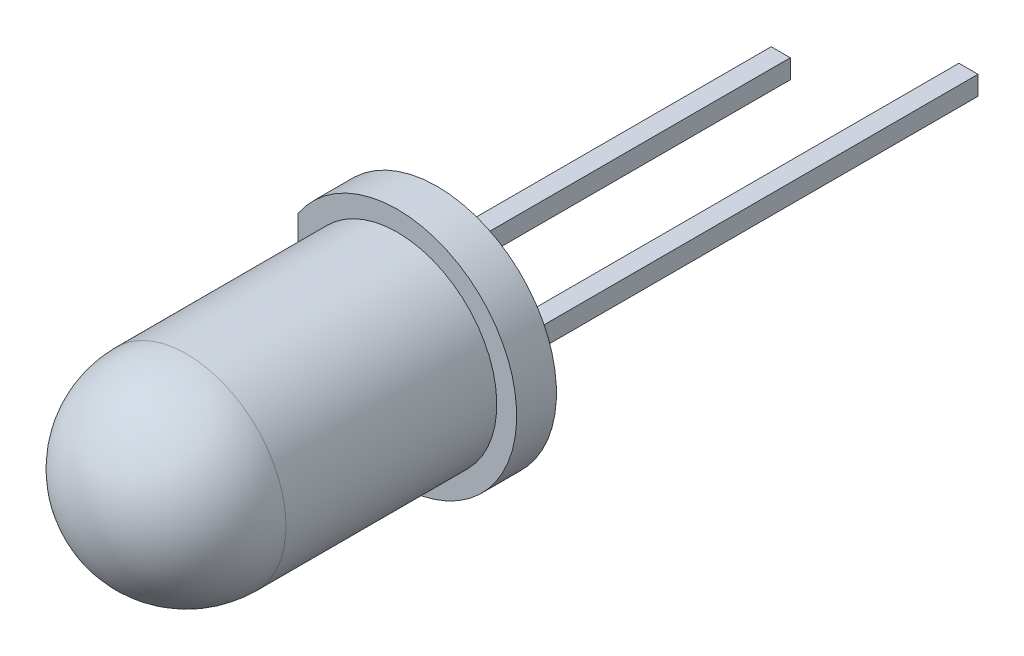
SolidWorks part; units mm, degrees
ref_plane "Plano frontal" through (0, 0, 0) normal (0, 0, 1) x (1, 0, 0)
ref_plane "Plano superior" through (0, 0, 0) normal (0, 1, 0) x (1, 0, 0)
ref_plane "Plano direito" through (0, 0, 0) normal (1, 0, 0) x (0, 0, -1)
sketch "Esboço1" plane through (0, 0, 0) normal (0, 0, 1) x (1, 0, 0)
  circle A0 centre (0, 0) radius 3
  dimension "D1" = 6
extrude "Ressalto-extrusão1" add sketch "Esboço1" along normal blind 1
sketch "Esboço3" plane through (0, 0, 0) normal (1, 0, 0) x (0, 0, -1)
  line L0 (-1, 0) -> (-8.8, 0)
  line L1 (-1, 3) -> (-1, -3) construction
  line L2 (-6.3, 2.5) -> (-1, 2.5)
  line L3 (-1, 0) -> (-1, 2.5)
  arc A0 (-8.8, 0) -> (-6.3, 2.5) centre (-6.3, 0) cw
  dimension "D1" = 2.5
  dimension "D2" = 7.8
revolve "Revolução1" add sketch "Esboço3" angle 360 about L0
sketch "Esboço4" plane through (0, 0, 0) normal (0, 0, -1) x (-1, 0, 0)
  line L0 (2.5, 1.6583) -> (2.5, -1.6583)
  circle A0 centre (0, 0) radius 3 construction
  arc A1 (2.5, -1.6583) -> (2.5, 1.6583) centre (0, 0) ccw
  circle A2 centre (0, 0) radius 2.5 construction
extrude "Corte-extrusão1" cut sketch "Esboço4" against normal up to surface (1 mm away) up to face at (2.5, 0, 1)
sketch "Esboço5" plane through (0, 0, 0) normal (0, 0, -1) x (-1, 0, 0)
  line L0 (-1.12, 0) -> (1.12, 0) construction
  line L1 (-1.6, -0.24) -> (-1.12, -0.24)
  line L2 (-1.6, -0.24) -> (-1.6, 0.24)
  line L3 (-1.6, 0.24) -> (-1.12, 0.24)
  line L4 (-1.12, -0.24) -> (-1.12, 0.24)
  line L5 (1.12, -0.24) -> (1.6, -0.24)
  line L6 (1.12, -0.24) -> (1.12, 0.24)
  line L7 (1.12, 0.24) -> (1.6, 0.24)
  line L8 (1.6, -0.24) -> (1.6, 0.24)
  dimension "D1" = 3.2
  dimension "D2" = 0.48
extrude "Ressalto-extrusão2" add sketch "Esboço5" along normal blind 10 separate body
sketch "Esboço6" plane through (0, 0, -10) normal (0, 0, -1) x (-1, 0, 0)
  line L4 (-1.6, 0.24) -> (-1.6, -0.24)
  line L5 (-1.6, -0.24) -> (-1.12, -0.24)
  line L6 (-1.12, -0.24) -> (-1.12, 0.24)
  line L7 (-1.12, 0.24) -> (-1.6, 0.24)
  line L8 (-1.6, 0.24) -> (-1.6, -0.24)
  line L9 (-1.6, -0.24) -> (-1.12, -0.24)
  line L10 (-1.12, -0.24) -> (-1.12, 0.24)
  line L11 (-1.12, 0.24) -> (-1.6, 0.24)
  dimension "D1" = 0
extrude "Ressalto-extrusão3" add sketch "Esboço6" along normal blind 2 separate body
sketch "Esboço7" plane through (0, 0, 0) normal (0, 1, 0) x (1, 0, 0)
  line L0 (-1.6, 0) -> (-1.6, -3.5)
  line L1 (-1.12, 0) -> (-1.12, -2)
  line L2 (0.02, -2) -> (1.2, -4)
  line L3 (1.2, -4) -> (-1.3, -4)
  line L4 (-1.3, -4) -> (-1.6, -3.5)
  line L5 (-1.12, -2) -> (0.02, -2)
  line L6 (1.6, 0) -> (1.6, -4)
  line L7 (1.6, -4) -> (1.4, -4)
  line L8 (1.4, -4) -> (0.22, -2)
  line L9 (0.22, -2) -> (1.12, -2)
  line L10 (1.12, -2) -> (1.12, 0)
  line L11 (-1.6, 0) -> (-1.12, 0)
  line L12 (1.12, 0) -> (1.6, 0)
  dimension "D1" = 4
  dimension "D2" = 2
  dimension "D3" = 2.8
  dimension "D4" = 0.2
  dimension "D5" = 0.9
  dimension "D6" = 3.5
  dimension "D7" = 2.5
extrude "Corte-extrusão2" cut sketch "Esboço7" against normal mid plane 0.48
sketch "Esboço8" plane through (0, 0, 0) normal (0, 1, 0) x (1, 0, 0)
  line L0 (-1.3, -4) -> (1.2, -4) construction
  line L1 (-1.6, -3.5) -> (-1.3, -4) construction
  line L2 (-1.6, 0) -> (-1.6, -3.5) construction
  line L3 (1.2, -4) -> (0.02, -2) construction
  line L4 (0.02, -2) -> (-1.12, -2) construction
  line L5 (-1.12, -2) -> (-1.12, 0) construction
  line L6 (0.22, -2) -> (1.4, -4) construction
  line L7 (1.12, -2) -> (0.22, -2) construction
  line L8 (1.12, 0) -> (1.12, -2) construction
  line L9 (1.6, -4) -> (1.6, 0) construction
  line L10 (1.4, -4) -> (1.6, -4) construction
  line L11 (-1.12, 0) -> (-1.6, 0) construction
  line L12 (1.6, 0) -> (1.12, 0) construction
  line L13 (-1.3, -4) -> (1.2, -4)
  line L14 (-1.6, -3.5) -> (-1.3, -4)
  line L15 (-1.6, 0) -> (-1.6, -3.5)
  line L16 (1.2, -4) -> (0.02, -2)
  line L17 (0.02, -2) -> (-1.12, -2)
  line L18 (-1.12, -2) -> (-1.12, 0)
  line L19 (0.22, -2) -> (1.4, -4)
  line L20 (1.12, -2) -> (0.22, -2)
  line L21 (1.12, 0) -> (1.12, -2)
  line L22 (1.6, -4) -> (1.6, 0)
  line L23 (1.4, -4) -> (1.6, -4)
  line L24 (-1.12, 0) -> (-1.6, 0)
  line L25 (1.6, 0) -> (1.12, 0)
extrude "Ressalto-extrusão4" add sketch "Esboço8" along normal mid plane 0.48 separate body
combine bodies "Combinar1" operation type add bodies to combine 109 106 104
combine bodies "Combinar2" operation type add bodies to combine 108 105
sketch "Esboço10" plane through (0, 0, 0) normal (0, 1, 0) x (1, 0, 0)
  line L0 (-0.05, -4) -> (-0.05, -3.7)
  line L1 (-1.3, -4) -> (1.2, -4) construction
  line L2 (-0.55, -4) -> (-0.05, -4)
  arc A0 (-0.05, -3.7) -> (-0.55, -4) centre (-0.05, -4.2667) ccw
  dimension "D1" = 0.5
  dimension "D2" = 0.3
revolve "Corte-Revolução1" cut sketch "Esboço10" angle 360 about L0
sketch "Esboço11" plane through (0, 0, 0) normal (0, 1, 0) x (1, 0, 0)
  line L0 (-0.55, -4) -> (-0.05, -4) construction
  line L1 (-0.05, -4) -> (-0.05, -3.7) construction
  line L2 (-0.55, -4) -> (-0.05, -4)
  line L3 (-0.05, -4) -> (-0.05, -3.7)
  arc A0 (-0.05, -3.7) -> (-0.55, -4) centre (-0.05, -4.2667) ccw construction
  arc A1 (-0.05, -3.7) -> (-0.55, -4) centre (-0.05, -4.2667) ccw
revolve "Revolução2" add sketch "Esboço11" angle 360 about L3
combine bodies "Combinar3" operation type add bodies to combine 113 112
sketch "Esboço12" plane through (0, 0, 4) normal (0, 0, 1) x (1, 0, 0)
  circle A0 centre (-0.05, 0) radius 0.2
  arc A1 (0.3886, 0.24) -> (-0.4886, 0.24) centre (-0.05, 0) ccw construction
  dimension "D1" = 0.4
extrude "Corte-extrusão3" cut sketch "Esboço12" against normal blind 0.1
sketch "Esboço13" plane through (0, 0, 0) normal (0, 1, 0) x (1, 0, 0)
  line L0 (1.6, 12) -> (-7.0603, 17)
  line L1 (1.6, 12) -> (1.12, 12) construction
  dimension "D1" = 10
  dimension "D2" = 30
ref_plane "Plano1" through (5.5962, 0, -9.6928) normal (0.5, 0, -0.866) x (-0.866, 0, -0.5)
